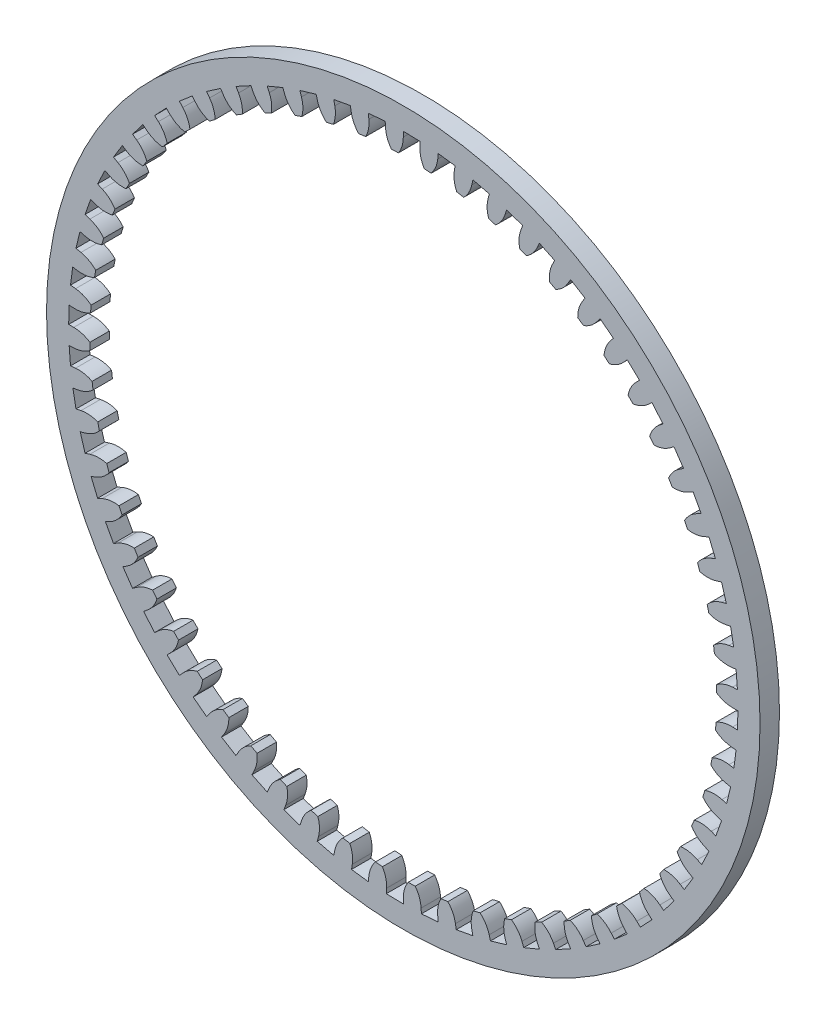
SolidWorks part; units mm, degrees
ref_plane "Ebene vorne (XY)" through (0, 0, 0) normal (0, 0, 1) x (1, 0, 0)
ref_plane "Ebene oben  (XZ)" through (0, 0, 0) normal (0, 1, 0) x (1, 0, 0)
ref_plane "Ebene rechts  (YZ)" through (0, 0, 0) normal (1, 0, 0) x (0, 0, -1)
ref_axis "x-Achse" through (-88.99, 0, 0) along (1, 0, 0)
ref_axis "y-Achse" through (0, 55, 0) along (0, -1, 0)
ref_axis "z-Achse" through (0, 0, -88.99) along (0, 0, 1)
sketch "Sketch1" plane through (0, 0, 0) normal (0, 0, 1) x (1, 0, 0)
  circle A0 centre (0, 0) radius 73.35
  circle A1 centre (0, 0) radius 64.57
  dimension "D1" = 129.14
  dimension "D2" = 146.7
sketch "Sketch2" plane through (0, 0, 0) normal (0, 0, 1) x (1, 0, 0)
  line L0 (-15.276, 71.8678) -> (0, 0) construction
  line L37 (0, 73.4734) -> (-15.276, 71.8678) construction
  line L38 (-15.276, 71.8678) -> (-29.8843, 67.1213) construction
  line L39 (-29.8843, 67.1213) -> (-43.1866, 59.4412) construction
  line L40 (-43.1866, 59.4412) -> (-54.6014, 49.1633) construction
  line L41 (-54.6014, 49.1633) -> (-63.6298, 36.7367) construction
  line L42 (-63.6298, 36.7367) -> (-69.8773, 22.7045) construction
  line L43 (-69.8773, 22.7045) -> (-73.0709, 7.6801) construction
  line L44 (-73.0709, 7.6801) -> (-73.0709, -7.6801) construction
  line L45 (-73.0709, -7.6801) -> (-69.8773, -22.7045) construction
  line L46 (-69.8773, -22.7045) -> (-63.6298, -36.7367) construction
  line L47 (-63.6298, -36.7367) -> (-54.6014, -49.1633) construction
  line L48 (-54.6014, -49.1633) -> (-43.1866, -59.4412) construction
  line L49 (-43.1866, -59.4412) -> (-29.8843, -67.1213) construction
  line L50 (-29.8843, -67.1213) -> (-15.276, -71.8678) construction
  line L51 (-15.276, -71.8678) -> (0, -73.4734) construction
  line L52 (0, -73.4734) -> (15.276, -71.8678) construction
  line L53 (15.276, -71.8678) -> (29.8843, -67.1213) construction
  line L54 (29.8843, -67.1213) -> (43.1866, -59.4412) construction
  line L55 (43.1866, -59.4412) -> (54.6014, -49.1633) construction
  line L56 (54.6014, -49.1633) -> (63.6298, -36.7367) construction
  line L57 (63.6298, -36.7367) -> (69.8773, -22.7045) construction
  line L58 (69.8773, -22.7045) -> (73.0709, -7.6801) construction
  line L59 (73.0709, -7.6801) -> (73.0709, 7.6801) construction
  line L60 (73.0709, 7.6801) -> (69.8773, 22.7045) construction
  line L61 (69.8773, 22.7045) -> (63.6298, 36.7367) construction
  line L62 (63.6298, 36.7367) -> (54.6014, 49.1633) construction
  line L63 (54.6014, 49.1633) -> (43.1866, 59.4412) construction
  line L64 (43.1866, 59.4412) -> (29.8843, 67.1213) construction
  line L65 (29.8843, 67.1213) -> (15.276, 71.8678) construction
  line L66 (15.276, 71.8678) -> (0, 73.4734) construction
  line L67 (0, 0) -> (0, 73.4734) construction
  line L68 (-10.8958, 68.0431) -> (-14.3272, 67.4042)
  line L69 (-14.3272, 67.4042) -> (-15.276, 71.8678)
  line L70 (-7.2031, 68.5325) -> (-3.7236, 68.8093)
  line L71 (-10.8958, 68.0431) -> (-10.2096, 63.7577)
  line L72 (0, 73.4734) -> (0, 64.57)
  line L73 (0, 64.57) -> (-3.4891, 64.4757)
  line L77 (-6.7494, 64.2163) -> (-10.2096, 63.7577)
  line L79 (-6.7494, 64.2163) -> (-7.2031, 68.5325)
  line L80 (-3.7236, 68.8093) -> (-3.4891, 64.4757)
  line L81 (-3.4891, 64.4757) -> (0, 0) construction
  line L82 (-10.2096, 63.7577) -> (0, 0) construction
  line L83 (-6.7494, 64.2163) -> (0, 0) construction
  circle A0 centre (0, 0) radius 73.0709 construction
  circle A1 centre (0, 0) radius 64.57 construction
  circle A2 centre (0, 0) radius 68.91 construction
  arc A3 (0, 73.4734) -> (-15.276, 71.8678) centre (0, 0) ccw
  point P3 (-3.7019, 68.5392)
  point P33 (-3.4825, 64.476)
  point P34 (-3.6737, 68.1874)
  point P35 (-3.654, 67.9407)
  dimension "D1" = 4.34
  dimension "D2" = 3.4904
extrude "Boss-Extrude1" add sketch "Sketch2" along normal blind 4 contours L72 A3 L69 L68 L71 L77 L79 L70 L80 L73 | L80 L73 L72 A3 L69 L68 L71 L77 L79 L70 region at (-6.7554, 69.3525, 0)
chamfer "Chamfer1" distance 1 angle 45 4 edges at (-3.4891, 64.4757, 2) (0, 64.57, 2) (-6.7494, 64.2163, 2) (-10.2096, 63.7577, 2) first distance on face at (-3.6064, 66.6425, 2) first distance on face at (-1.7446, 64.5228, 2) first distance on face at (-8.4795, 63.987, 2) first distance on face at (-10.5527, 65.9004, 2)
fillet "Fillet1" radius 6 4 edges at (0, 65.5982, 2) (-3.5432, 65.4742, 2) (-6.8569, 65.2388, 2) (-10.3677, 64.7452, 2)
ref_axis "Axis1" through (0, 0, -0.2) along (0, 0, 1)
pattern_circular "CirPattern6" count 30 over 360 about axis through (0, 0, -0.2) along (0, 0, 1) of "Boss-Extrude1", "Chamfer1", "Fillet1"
